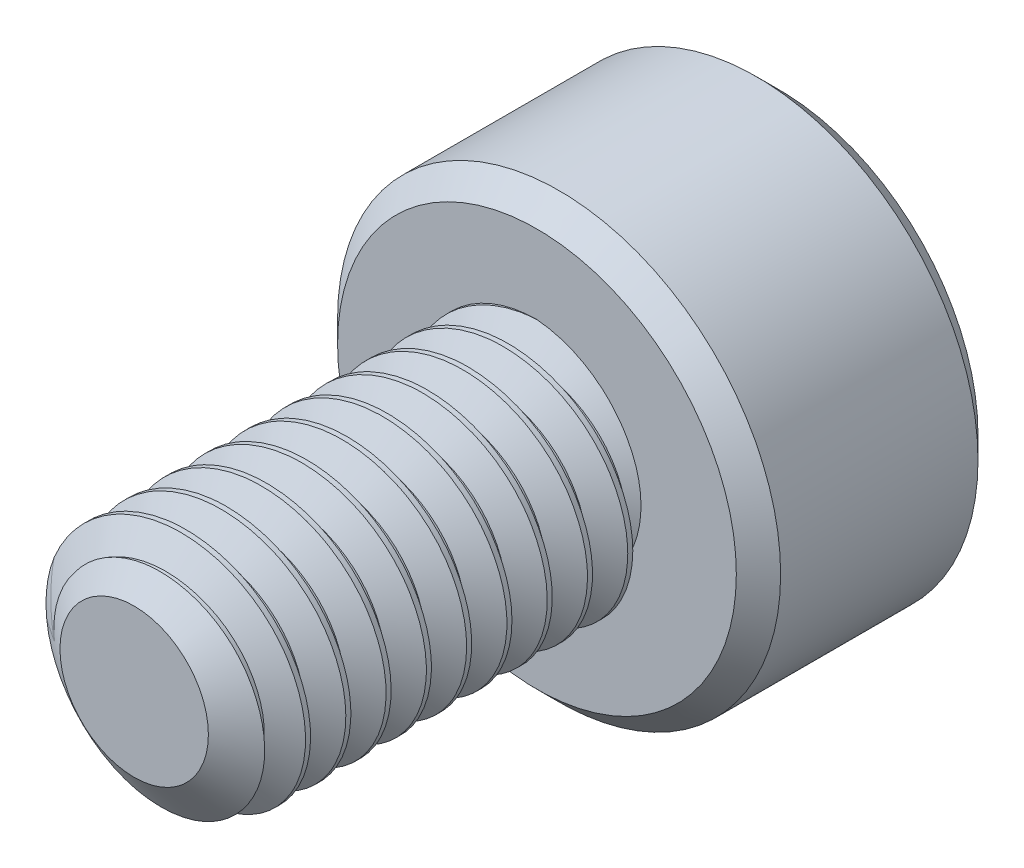
SolidWorks part; units mm, degrees
ref_plane "Front Plane" through (0, 0, 0) normal (0, 0, 1) x (1, 0, 0)
ref_plane "Top Plane" through (0, 0, 0) normal (0, 1, 0) x (1, 0, 0)
ref_plane "Right Plane" through (0, 0, 0) normal (1, 0, 0) x (0, 0, -1)
sketch "Sketch1" plane through (0, 0, 0) normal (0, 0, 1) x (1, 0, 0)
  circle A0 centre (0, 0) radius 1.5
  dimension "OD" = 3
extrude "Extrude1" add sketch "Sketch1" against normal blind 5
sketch "Sketch2" plane through (0, 0, 0) normal (0, 0, 1) x (1, 0, 0)
  circle A0 centre (0, 0) radius 1.5 construction
  circle A1 centre (0, 0) radius 1.5
curve "Helix/Spiral1" pitch 0.5 height 5.5 radius 1.5 centre (0, 0, 0) axis (0, 0, -1) start towards (0, 1, 0) parameters "pitch"=0.5
sketch "Sketch3" plane through (0, 0, 0) normal (1, 0, 0) x (0, 0, -1)
  line L0 (-0.4375, 1.5) -> (-0.25, 1.1752)
  line L1 (-0.25, 1.1752) -> (-0.1875, 1.1752)
  line L2 (-0.1875, 1.1752) -> (0, 1.5)
  line L3 (-0.4375, 1.5) -> (0, 1.5)
  line L4 (-0.2187, 1.5) -> (-0.2187, 1.1752) construction
  line L5 (-0.3437, 1.3376) -> (-0.0937, 1.3376) construction
  line L6 (0, 1.5) -> (0, -1.5) construction
  dimension "D1" = 0.0625
  dimension "D2" = 0.25
  dimension "D3" = 60
sweep "Cut-Sweep1" cut profiles "Sketch3" path "Helix/Spiral1"
sketch "Sketch4" plane through (0, 0, 0) normal (1, 0, 0) x (0, 0, -1)
  line L0 (0.4053, 1.5) -> (0, 0.9212)
  line L1 (0, 0.9212) -> (0, 1.5)
  line L2 (0.4053, 1.5) -> (0, 1.5)
  line L3 (-0.4375, 1.5) -> (0, 1.5) construction
  line L4 (0, 0) -> (7.0209, 0) construction
  dimension "D1" = 55
  dimension "D2" = 0.254
revolve "Cut-Revolve1" cut sketch "Sketch4" angle 360 about L4
sketch "Sketch5" plane through (0, 0, 0) normal (1, 0, 0) x (0, 0, -1)
  line L0 (5, -1.1822) -> (5, 1.0703) construction
  line L1 (5, 1.627) -> (87.4327, 1.627)
  line L2 (5, 1.627) -> (5, 0)
  line L3 (5, 0) -> (87.3125, 0)
  line L4 (87.3125, 1.2968) -> (87.3125, 0)
  line L5 (87.4327, 1.627) -> (87.3125, 1.2968)
  line L6 (0, 0) -> (9.9695, 0) construction
  point P3 (87.3125, 1.627)
  point P10 (87.3125, 1.627)
  dimension "D1" = 0.3302
  dimension "Thread min" = 87.3125
  dimension "D2" = 0.127
  dimension "D3" = 20
revolve "partially thread" [suppressed] add sketch "Sketch5" angle 360 about L6
sketch "Sketch6" plane through (0, 0, -5) normal (0, 0, -1) x (-1, 0, 0)
  circle A0 centre (0, 0) radius 2.75
  dimension "head dia" = 5.5
extrude "Extrude2" add sketch "Sketch6" along normal blind 3
sketch "Sketch7" plane through (0, 0, -8) normal (0, 0, -1) x (-1, 0, 0)
  line L1 (0, 1.4434) -> (-1.25, 0.7217)
  line L2 (-1.25, 0.7217) -> (-1.25, -0.7217)
  line L3 (-1.25, -0.7217) -> (0, -1.4434)
  line L4 (0, -1.4434) -> (1.25, -0.7217)
  line L5 (1.25, -0.7217) -> (1.25, 0.7217)
  line L6 (1.25, 0.7217) -> (0, 1.4434)
  circle A0 centre (0, 0) radius 1.25 construction
  dimension "hex dia" = 2.5
extrude "Cut-Extrude1" cut sketch "Sketch7" against normal blind 1.875
sketch "Sketch8" plane through (0, 0, -8) normal (0, 0, -1) x (-1, 0, 0)
  circle A0 centre (0, 0) radius 1.4434
extrude "Cut-Extrude2" cut sketch "Sketch8" against normal through all draft 45
chamfer "Chamfer1" distance 0.275 angle 45 2 edges at (-2.75, 0, -8) (-2.75, 0, -5)
sketch "Sketch9" plane through (0, 0, 0) normal (1, 0, 0) x (0, 0, -1)
  line L0 (0, 1.5) -> (0, -1.5) construction
  line L1 (2.75, 1.5) -> (2.75, -1.5) construction
  dimension "D1" = 2.75
equation "\"D3@Helix/Spiral1\" = \"screw length@Extrude1\"+\"pitch@Helix/Spiral1\""
equation "\"D1@Sketch3\" = \"pitch@Helix/Spiral1\"*.125"
equation "\"D2@Sketch3\" = \"pitch@Helix/Spiral1\"*.5"
equation "\"D1@Cut-Extrude1\" = \"hex dia@Sketch7\"*.75"
equation "\"D1@Chamfer1\" = \"head dia@Sketch6\"*.05"
equation "\"D1@Sketch9\" = \"pitch@Helix/Spiral1\"*5.5"
